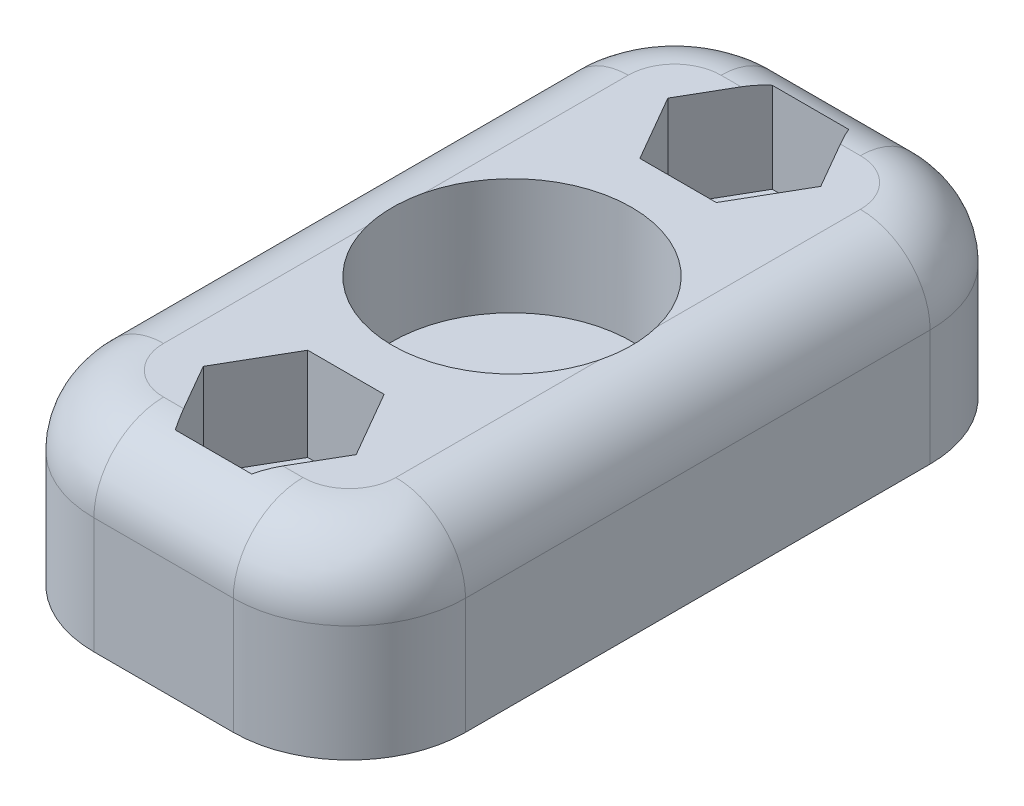
SolidWorks part; units mm, degrees
ref_plane "Plan de face" through (0, 0, 0) normal (0, 0, 1) x (1, 0, 0)
ref_plane "Plan de dessus" through (0, 0, 0) normal (0, 1, 0) x (1, 0, 0)
ref_plane "Plan de droite" through (0, 0, 0) normal (1, 0, 0) x (0, 0, -1)
sketch "Esquisse1" plane through (0, 0, 0) normal (0, 1, 0) x (1, 0, 0)
  line L0 (8, 30) -> (8, 0) construction
  line L1 (0, 0) -> (16, 0)
  line L2 (0, 0) -> (0, 30)
  line L3 (0, 30) -> (16, 30)
  line L4 (16, 0) -> (16, 30)
  line L5 (0, 15) -> (16, 15) construction
  circle A0 centre (8, 25) radius 1.75
  circle A1 centre (8, 5) radius 1.75
  dimension "D4" = 3.5
  dimension "D1" = 16
  dimension "D2" = 30
  dimension "D3" = 5
extrude "Boss.-Extru.1" add sketch "Esquisse1" along normal blind 8
sketch "Esquisse2" plane through (0, 8, 0) normal (0, 1, 0) x (1, 0, 0)
  line L0 (0, 30) -> (16, 0) construction
  circle A0 centre (8, 15) radius 5.15
  dimension "D1" = 10.3
extrude "Enlèv. mat.-Extru.1" cut sketch "Esquisse2" against normal blind 5
fillet "Congé1" radius 5 4 edges at (0, 4, 0) (16, 4, 0) (0, 4, -30) (16, 4, -30)
sketch "Esquisse3" plane through (0, 8, 0) normal (0, 1, 0) x (1, 0, 0)
  line L0 (6.3546, 27.85) -> (9.6454, 27.85)
  line L1 (9.6454, 27.85) -> (11.2909, 25)
  line L2 (11.2909, 25) -> (9.6454, 22.15)
  line L3 (9.6454, 22.15) -> (6.3546, 22.15)
  line L4 (6.3546, 22.15) -> (4.7091, 25)
  line L5 (4.7091, 25) -> (6.3546, 27.85)
  line L6 (4.7091, 25) -> (11.2909, 25) construction
  line L7 (6.3546, 7.85) -> (9.6454, 7.85)
  line L8 (9.6454, 7.85) -> (11.2909, 5)
  line L9 (11.2909, 5) -> (9.6454, 2.15)
  line L10 (9.6454, 2.15) -> (6.3546, 2.15)
  line L11 (6.3546, 2.15) -> (4.7091, 5)
  line L12 (4.7091, 5) -> (6.3546, 7.85)
  line L13 (4.7091, 5) -> (11.2909, 5) construction
  point P2 (8, 25)
  point P7 (8, 5)
  point P16 (8, 25)
  point P17 (8, 5)
  dimension "D1" = 120
  dimension "D2" = 5.7
  dimension "D3" = 120
  dimension "D4" = 5.7
extrude "Enlèv. mat.-Extru.2" cut sketch "Esquisse3" against normal blind 4
fillet "Congé2" radius 3 8 edges at (1.4645, 8, -1.4645) (0, 8, -15) (1.4645, 8, -28.5355) (8, 8, -30) (14.5355, 8, -28.5355) (16, 8, -15) (14.5355, 8, -1.4645) (8, 8, 0)
